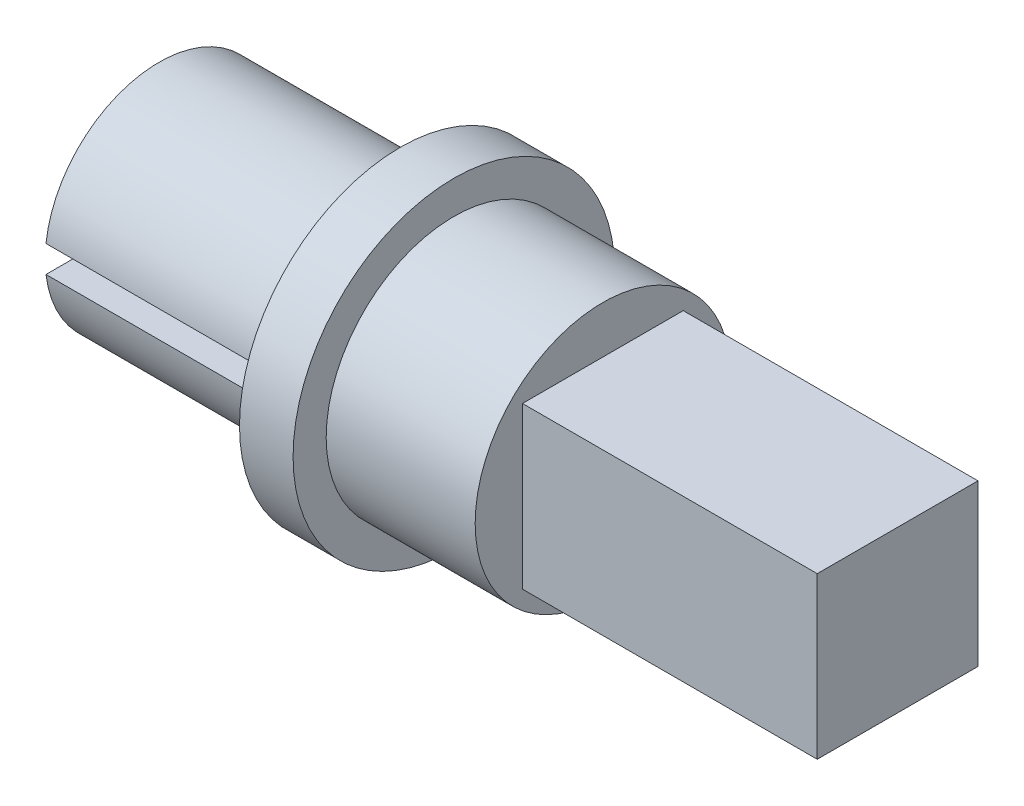
SolidWorks part; units mm, degrees
ref_plane "Front Plane" through (0, 0, 0) normal (0, 0, 1) x (1, 0, 0)
ref_plane "Top Plane" through (0, 0, 0) normal (0, 1, 0) x (1, 0, 0)
ref_plane "Right Plane" through (0, 0, 0) normal (1, 0, 0) x (0, 0, -1)
sketch "Sketch1" plane through (0, 0, 0) normal (1, 0, 0) x (0, 0, -1)
  circle A0 centre (0, 0) radius 4.765
  dimension "D1" = 9.53
extrude "Boss-Extrude1" add sketch "Sketch1" along normal mid plane 5.56
sketch "Sketch2" plane through (-2.78, 0, 0) normal (-1, 0, 0) x (0, 0, 1)
  circle A1 centre (0, 0) radius 2.85 construction
  circle A2 centre (0, 0) radius 4.25
  dimension "D1" = 5.7
  dimension "D2" = 8.5
extrude "Boss-Extrude2" add sketch "Sketch2" along normal blind 11
sketch "Sketch3" plane through (2.78, 0, 0) normal (1, 0, 0) x (0, 0, -1)
  line L1 (-3, 3) -> (3, 3)
  line L2 (-3, 3) -> (-3, -3)
  line L3 (-3, -3) -> (3, -3)
  line L4 (3, 3) -> (3, -3)
  line L5 (-3, 3) -> (3, -3) construction
  line L6 (-3, -3) -> (3, 3) construction
  point P0 (0, 0)
  dimension "D1" = 6
extrude "Boss-Extrude3" add sketch "Sketch3" along normal blind 11
sketch "Sketch4" plane through (-2.78, 0, 0) normal (-1, 0, 0) x (0, 0, 1)
  line L0 (-4.25, 0) -> (4.25, 0) construction
  circle A0 centre (0, 0) radius 4.25 construction
  circle A1 centre (0, 0) radius 4.25 construction
  circle A2 centre (0, 0) radius 2.85
  dimension "D1" = 5.7
extrude "Cut-Extrude1" cut sketch "Sketch4" against normal up to surface from surface up to face at (-2.78, 0, 4.25) starting at face at (-13.78, 0, 4.25)
sketch "Sketch5" plane through (-13.78, 0, 0) normal (-1, 0, 0) x (0, 0, 1)
  line L0 (-4.765, 0) -> (4.765, 0) construction
  line L1 (-4.765, -0.5) -> (4.765, -0.5)
  line L2 (-4.765, 0.5) -> (4.765, 0.5)
  circle A0 centre (0, 0) radius 4.765 construction
  arc A1 (-4.7387, 0.5) -> (-4.7387, -0.5) centre (0, 0) ccw
  arc A2 (4.7387, 0.5) -> (-4.7387, 0.5) centre (0, 0) ccw construction
  arc A3 (-4.7387, -0.5) -> (4.7387, -0.5) centre (0, 0) ccw construction
  arc A4 (4.7387, -0.5) -> (4.7387, 0.5) centre (0, 0) ccw
  circle M2 centre (0, 0) radius 2.85
  circle M3 centre (0, 0) radius 4.25
  dimension "D1" = 0.5
  dimension "D2" = 0.5
extrude "Cut-Extrude2" cut sketch "Sketch5" against normal blind 10 contours L2 L1 M3 M2 | L2 A1 L1 M3 | L2 L1 M2 | L2 L1 M2 M3 | L1 A4 L2 M3 region at (-13.78, 0, -4.4982) region at (-13.78, 0, -3.5377) region at (-13.78, 0, 0) region at (-13.78, 0, 4.4982) region at (-13.78, 0, 3.5377)
sketch "Sketch6" plane through (-13.78, 0, 0) normal (-1, 0, 0) x (0, 0, 1)
  line L1 (1.6454, -2.85) -> (3.2909, 0)
  line L2 (3.2909, 0) -> (1.6454, 2.85)
  line L3 (1.6454, 2.85) -> (-1.6454, 2.85)
  line L4 (-1.6454, 2.85) -> (-3.2909, 0)
  line L5 (-3.2909, 0) -> (-1.6454, -2.85)
  line L6 (-1.6454, -2.85) -> (1.6454, -2.85)
  circle A0 centre (0, 0) radius 2.85 construction
  circle A1 centre (0, 0) radius 2.85 construction
  point P11 (0, 0)
extrude "Cut-Extrude3" cut sketch "Sketch6" against normal up to surface (11 mm away) and the other way through all up to face at (-2.78, 0, 4.25)
sketch "Sketch7" plane through (-2.78, 0, 0) normal (-1, 0, 0) x (0, 0, 1)
  line L0 (-6, 0) -> (0, 0) construction
  circle A0 centre (0, 0) radius 6
  dimension "D1" = 12
extrude "Boss-Extrude5" add sketch "Sketch7" along normal blind 2 contours A0
equation "\"ID\"= 9.53mm"
equation "\"ID_Extension\"= 11mm"
equation "\"ServoHorn\"= 5.7mm"
equation "\"CarrierLength\"= 10mm"
equation "\"D1@Sketch1\"=\"ID\""
equation "\"ID_Bearing\"= 5.56mm"
equation "\"D1@Boss-Extrude1\"=\"ID_Bearing\""
equation "\"D1@Sketch2\"=\"ServoHorn\""
equation "\"D1@Boss-Extrude2\"=\"ID_Extension\""
equation "\"D1@Sketch4\"=\"ServoHorn\""
